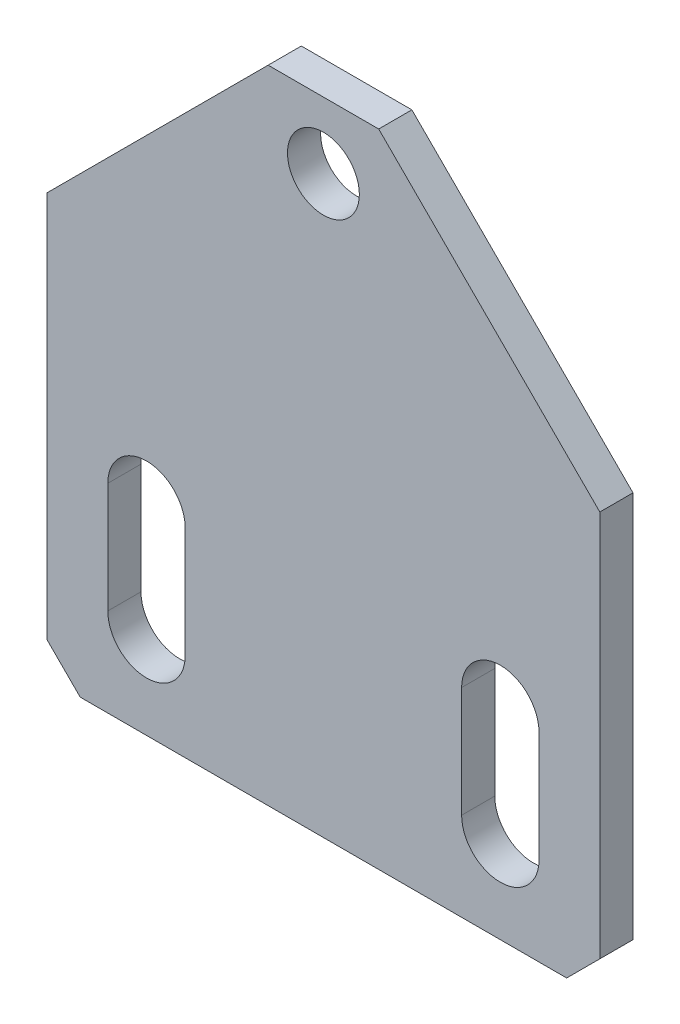
SolidWorks part; units mm, degrees
material "Q235-A"
ref_plane "前视基准面" through (0, 0, 0) normal (0, 0, 1) x (1, 0, 0)
ref_plane "上视基准面" through (0, 0, 0) normal (0, 1, 0) x (1, 0, 0)
ref_plane "右视基准面" through (0, 0, 0) normal (1, 0, 0) x (0, 0, -1)
sketch "草图1" plane through (0, 0, 0) normal (0, 0, 1) x (1, 0, 0)
  line L1 (25, -29) -> (-25, -29)
  line L2 (25, -29) -> (25, 29)
  line L3 (25, 29) -> (-25, 29)
  line L4 (-25, -29) -> (-25, 29)
  line L5 (25, -29) -> (-25, 29) construction
  line L6 (25, 29) -> (-25, -29) construction
  point P0 (0, 0)
  dimension "D1" = 58
  dimension "D2" = 50
base flange "基体-法兰1" sketch "草图1" thickness 3 reverse thickness direction no parameters "D1"=0.7366
sketch "草图2" plane through (0, 0, 0) normal (0, 0, 1) x (1, 0, 0)
  line L0 (25, 29) -> (-25, 29) construction
  circle A0 centre (0, 23) radius 3.25
  dimension "D1" = 6.5
  dimension "D2" = 6
extrude "切除-拉伸1" cut sketch "草图2" against normal blind 10 normal cut yes
hole_wizard "Ø7.0 (7) 直径孔1" positions "草图3" profile "草图4" hole size "Ø7.0" standard "GB" end condition through all
sketch "草图3" plane through (0, 0, 0) normal (0, 0, 1) x (1, 0, 0)
  line L0 (-25, -29) -> (25, -29) construction
  point P0 (-16, -11.5)
  point P2 (16, -11.5)
  dimension "D1" = 32
  dimension "D2" = 16
  dimension "D3" = 17.5
sketch "草图4" plane through (-16, -11.5, 0) normal (1, 0, 0) x (0, -1, 0)
  line L0 (0, 0) -> (0, 3)
  line L1 (0, 3) -> (3.5, 3)
  line L2 (3.5, 3) -> (3.5, 0)
  line L5 (3.5, 0) -> (0, 0)
  line L11 (0, -6.35) -> (0, 107.95) construction
  dimension "通孔孔直径" = 7
  dimension "通孔孔深度" = 3
chamfer "倒角1" distance 3 angle 45 2 edges at (-25, -29, -1.5) (25, -29, -1.5)
sketch "草图5" plane through (0, 0, 0) normal (0, 0, 1) x (1, 0, 0)
  line L0 (-5, 29) -> (-25, 9)
  line L1 (25, 29) -> (-25, 29) construction
  line L2 (-25, 29) -> (-25, -26) construction
  line L3 (-25, 9) -> (-25, 29)
  line L4 (-25, 29) -> (-5, 29)
  line L5 (25, 29) -> (5, 29)
  line L6 (5, 29) -> (25, 9)
  line L7 (25, -26) -> (25, 29) construction
  line L8 (25, 9) -> (25, 29)
  dimension "D1" = 20
  dimension "D2" = 20
  dimension "D3" = 20
  dimension "D4" = 20
extrude "切除-拉伸2" cut sketch "草图5" against normal blind 10 normal cut yes
sketch "草图7" plane through (0, 0, 0) normal (0, 0, 1) x (1, 0, 0)
  line L0 (-16, -21) -> (-16, -11) construction
  line L1 (-19.5, -21) -> (-19.5, -11)
  line L2 (-12.5, -21) -> (-12.5, -11)
  line L3 (16, -21) -> (16, -11) construction
  line L4 (12.5, -21) -> (12.5, -11)
  line L5 (19.5, -21) -> (19.5, -11)
  line L6 (-22, -29) -> (22, -29) construction
  arc A0 (-19.5, -21) -> (-12.5, -21) centre (-16, -21) ccw
  arc A1 (-12.5, -11) -> (-19.5, -11) centre (-16, -11) ccw
  arc A2 (12.5, -21) -> (19.5, -21) centre (16, -21) ccw
  arc A3 (19.5, -11) -> (12.5, -11) centre (16, -11) ccw
  point P2 (-16, -16)
  point P9 (16, -16)
  point P16 (-16, -13.5866)
  point P17 (16, -10.5)
  point P18 (15.9661, -13.5866)
  point P21 (19.3907, -20)
  dimension "D1" = 7
  dimension "D2" = 7
  dimension "D3" = 10
  dimension "D4" = 10
  dimension "D5" = 8
  dimension "D6" = 32
extrude "切除-拉伸3" cut sketch "草图7" against normal blind 10 normal cut yes
sketch "折弯-线1" [suppressed] plane through (0, 0, 0) normal (0, 1, 0) x (1, 0, 0)
sketch "边界框1" [suppressed] plane through (0, 0, 0) normal (0, 1, 0) x (1, 0, 0)
sheet metal parameters "钣金1" thickness 3 parameters "D1"=0.7366
flat pattern "平板型式1" [suppressed]
sketch "折弯-线2" plane through (0, 0, 0) normal (0, 1, 0) x (1, 0, 0)
sketch3d "边界框2" [suppressed]
  line L0 (10, 20, 0) -> (10, -20, 0) construction
  line L1 (-10, 20, 0) -> (-10, -20, 0) construction
  line L2 (10, 20, 0) -> (-10, 20, 0) construction
  line L3 (10, -20, 0) -> (-10, -20, 0) construction
sheet metal parameters "钣金5" thickness 3 parameters "D1"=0.7366
flat pattern "平板型式1"
sketch "折弯-线2" plane through (0, 0, 0) normal (0, 1, 0) x (1, 0, 0)
sketch3d "边界框2" [suppressed]
  line L0 (25, 30, 0) -> (25, -30, 0) construction
  line L1 (-25, 30, 0) -> (-25, -30, 0) construction
  line L2 (25, 30, 0) -> (-25, 30, 0) construction
  line L3 (25, -30, 0) -> (-25, -30, 0) construction
sheet metal parameters "钣金6" thickness 3 parameters "D1"=0.7366
flat pattern "平板型式1"
sketch "折弯-线2" plane through (0, 0, 0) normal (0, 1, 0) x (1, 0, 0)
sketch3d "边界框2" [suppressed]
  line L0 (25, 30, 0) -> (25, -30, 0) construction
  line L1 (-25, 30, 0) -> (-25, -30, 0) construction
  line L2 (25, 30, 0) -> (-25, 30, 0) construction
  line L3 (25, -30, 0) -> (-25, -30, 0) construction
sheet metal parameters "钣金7" thickness 3 parameters "D1"=0.7366
flat pattern "平板型式1"
sketch "折弯-线2" plane through (0, 0, 0) normal (0, 1, 0) x (1, 0, 0)
sketch3d "边界框2" [suppressed]
  line L0 (25, 28, 0) -> (25, -28, 0) construction
  line L1 (-25, 28, 0) -> (-25, -28, 0) construction
  line L2 (25, 28, 0) -> (-25, 28, 0) construction
  line L3 (25, -28, 0) -> (-25, -28, 0) construction
sheet metal parameters "钣金8" thickness 3 parameters "D1"=0.7366
flat pattern "平板型式1"
sketch "折弯-线2" plane through (0, 0, 0) normal (0, 1, 0) x (1, 0, 0)
sketch3d "边界框2" [suppressed]
  line L0 (25, 29, 0) -> (25, -29, 0) construction
  line L1 (-25, 29, 0) -> (-25, -29, 0) construction
  line L2 (25, 29, 0) -> (-25, 29, 0) construction
  line L3 (25, -29, 0) -> (-25, -29, 0) construction
